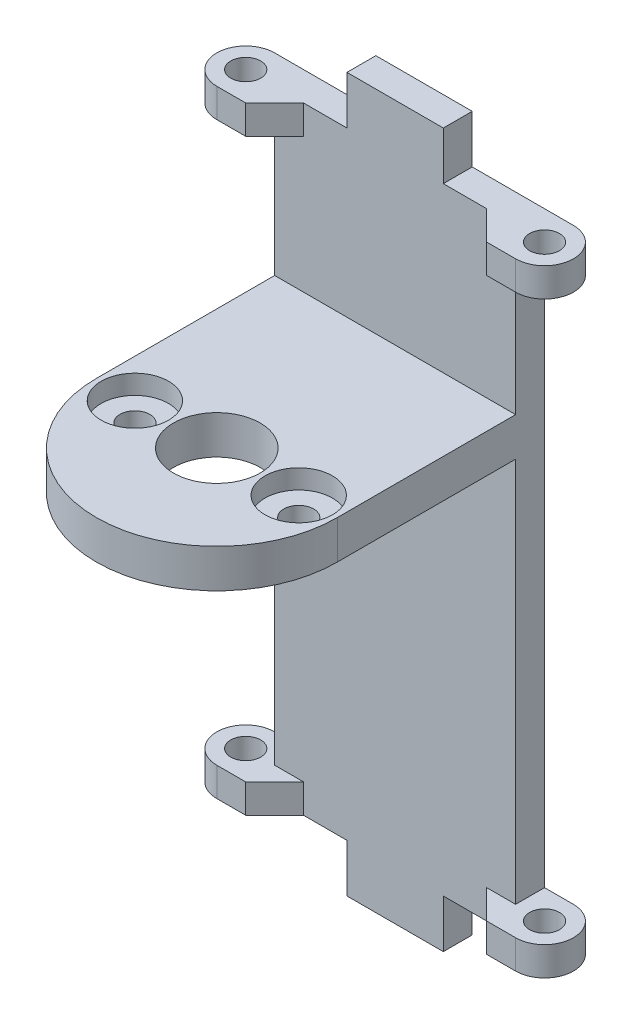
SolidWorks part; units mm, degrees
ref_plane "Front Plane" through (0, 0, 0) normal (0, 0, 1) x (1, 0, 0)
ref_plane "Top Plane" through (0, 0, 0) normal (0, 1, 0) x (1, 0, 0)
ref_plane "Right Plane" through (0, 0, 0) normal (1, 0, 0) x (0, 0, -1)
sketch "Sketch11" plane through (0, 0, 51.65) normal (0, -1, 0) x (1, 0, 0)
  line L0 (12.5, 90) -> (12.5, 71.5)
  line L1 (-12.5, 90) -> (-12.5, 71.5)
  line L6 (-12.5, 71.5) -> (12.5, 71.5)
  circle A0 centre (-8.5, 90) radius 1.55
  circle A1 centre (8.5, 90) radius 1.55
  circle A4 centre (0, 90) radius 4.5
  arc A5 (-12.5, 90) -> (12.5, 90) centre (0, 90) cw
extrude "Boss-Extrude1" add sketch "Sketch11" along normal blind 4
sketch "Sketch12" plane through (0, 0, 123.15) normal (0, 0, -1) x (-1, 0, 0)
  line L0 (-12.5, 0) -> (-12.5, 17)
  line L1 (12.5, 0) -> (12.5, 17)
  line L3 (-12.5, 0) -> (-12.5, -4)
  line L4 (-12.5, -4) -> (-12.5, -47)
  line L5 (12.5, 0) -> (12.5, -4)
  line L6 (12.5, -4) -> (12.5, -47)
  line L8 (-12.5, 17) -> (-5, 17)
  line L9 (-5, 17) -> (-5, 22)
  line L12 (5, 17) -> (12.5, 17)
  line L13 (-5, 22) -> (5, 22)
  line L14 (5, 22) -> (5, 17)
  line L15 (-12.5, -47) -> (-5, -47)
  line L16 (-5, -47) -> (-5, -52)
  line L17 (-5, -52) -> (5, -52)
  line L18 (5, -52) -> (5, -47)
  line L19 (5, -47) -> (12.5, -47)
extrude "Boss-Extrude2" add sketch "Sketch12" along normal blind 3
sketch "Sketch13" plane through (0, 0, 0) normal (0, 1, 0) x (1, 0, 0)
  circle A0 centre (-8.5, -141.65) radius 3.5
  circle A1 centre (8.5, -141.65) radius 3.5
extrude "Cut-Extrude1" cut sketch "Sketch13" against normal blind 2
ref_plane "Plane1" through (0, 17, 0) normal (0, 1, 0) x (1, 0, 0)
sketch "Sketch14" plane through (0, 17, 0) normal (0, 1, 0) x (1, 0, 0)
  line L0 (12.5, -123.15) -> (15.5, -123.15) construction
  line L1 (-12.5, -141.65) -> (-12.5, -123.15) construction
  line L2 (-12.5, -123.15) -> (-15.5, -123.15) construction
  line L3 (5, -123.15) -> (12.5, -123.15) construction
  line L4 (12.5, -123.15) -> (12.5, -141.65) construction
  line L6 (15.5, -120.15) -> (-15.5, -120.15)
  line L7 (-15.5, -126.15) -> (-12.5, -126.15)
  line L11 (12.5, -126.15) -> (15.5, -126.15)
  line L12 (-12.5, -126.15) -> (-9.5, -123.15)
  line L13 (12.5, -126.15) -> (9.5, -123.15)
  line L15 (-12.5, -123.15) -> (12.5, -123.15) construction
  line L16 (9.5, -123.15) -> (-9.5, -123.15)
  arc A0 (-15.5, -120.15) -> (-15.5, -126.15) centre (-15.5, -123.15) ccw
  circle A1 centre (-15.5, -123.15) radius 1.55
  circle A2 centre (15.5, -123.15) radius 1.55
  arc A3 (15.5, -120.15) -> (15.5, -126.15) centre (15.5, -123.15) cw
extrude "Boss-Extrude3" add sketch "Sketch14" against normal blind 3
ref_plane "Plane2" through (0, -47, 0) normal (0, -1, 0) x (-1, 0, 0)
sketch "Sketch15" plane through (0, -47, 0) normal (0, -1, 0) x (-1, 0, 0)
  line L0 (15.5, -126.15) -> (12.5, -126.15) construction
  line L1 (15.5, -120.15) -> (-15.5, -120.15)
  line L2 (-15.5, -126.15) -> (-12.5, -126.15)
  line L3 (-12.5, -126.15) -> (-9.5, -123.15)
  line L4 (-12.5, -123.15) -> (-5, -123.15) construction
  line L5 (15.5, -126.15) -> (12.5, -126.15)
  line L6 (12.5, -126.15) -> (9.5, -123.15)
  line L7 (5, -123.15) -> (12.5, -123.15) construction
  line L8 (9.5, -123.15) -> (-9.5, -123.15)
  circle A0 centre (15.5, -123.15) radius 1.55
  circle A1 centre (-15.5, -123.15) radius 1.55
  arc A2 (15.5, -120.15) -> (15.5, -126.15) centre (15.5, -123.15) cw
  arc A3 (-15.5, -120.15) -> (-15.5, -126.15) centre (-15.5, -123.15) ccw
  arc A4 (-15.5, -120.15) -> (-15.5, -126.15) centre (-15.5, -123.15) ccw construction
extrude "Boss-Extrude4" add sketch "Sketch15" against normal blind 3
